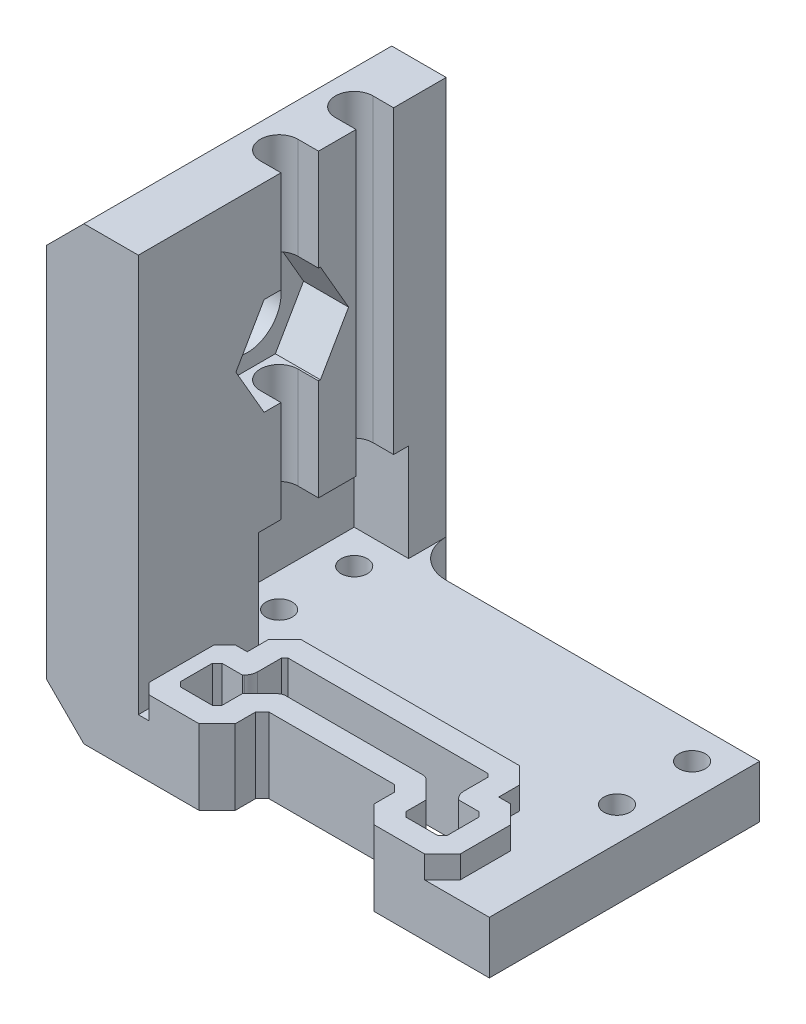
SolidWorks part; units mm, degrees
ref_plane "Front Plane" through (0, 0, 0) normal (0, 0, 1) x (1, 0, 0)
ref_plane "Top Plane" through (0, 0, 0) normal (0, 1, 0) x (1, 0, 0)
ref_plane "Right Plane" through (0, 0, 0) normal (1, 0, 0) x (0, 0, -1)
ref_plane "Plane1" through (0, 200, 0) normal (0, 1, 0) x (1, 0, 0)
sketch "Sketch1" plane through (0, 200, 0) normal (0, 1, 0) x (1, 0, 0)
  line L0 (0, -3.8557) -> (0.25, -4)
  line L1 (0.25, -4) -> (9.0787, -4)
  line L2 (10.1394, -4.4394) -> (12.5, -6.8)
  line L3 (12.5, -6.8) -> (12.5, -9.5)
  line L4 (12.5, -9.5) -> (13, -10)
  line L5 (13, -10) -> (17, -10)
  line L6 (17, -10) -> (17.5, -9.5)
  line L7 (17.5, -9.5) -> (17.5, -5.5)
  line L8 (17.5, -5.5) -> (17, -5)
  line L9 (17, -5) -> (14.3, -5)
  line L10 (14.3, -5) -> (14.0858, -4.7858)
  line L11 (13.5, -3.3716) -> (13.5, -0.3)
  line L12 (13.5, -0.3) -> (13.2, 0)
  line L13 (13.2, 0) -> (7.5, 0)
  line L14 (7.5, 0) -> (7.4, -0.1)
  line L15 (7.4, -0.1) -> (-7.4, -0.1)
  line L16 (-7.4, -0.1) -> (-7.5, 0)
  line L17 (-7.5, 0) -> (-13.2, 0)
  line L18 (-13.2, 0) -> (-13.5, -0.3)
  line L19 (-13.5, -0.3) -> (-13.5, -3.3716)
  line L20 (-14.0858, -4.7858) -> (-14.3, -5)
  line L21 (-14.3, -5) -> (-17, -5)
  line L22 (-17, -5) -> (-17.5, -5.5)
  line L23 (-17.5, -5.5) -> (-17.5, -9.5)
  line L24 (-17.5, -9.5) -> (-17, -10)
  line L25 (-17, -10) -> (-13, -10)
  line L26 (-13, -10) -> (-12.5, -9.5)
  line L27 (-12.5, -9.5) -> (-12.5, -6.8)
  line L28 (-12.5, -6.8) -> (-10.1394, -4.4394)
  line L29 (-9.0787, -4) -> (-0.25, -4)
  line L30 (-0.25, -4) -> (0, -3.8557)
  arc A0 (9.0787, -4) -> (10.1394, -4.4394) centre (9.0787, -5.5) cw
  arc A1 (14.0858, -4.7858) -> (13.5, -3.3716) centre (15.5, -3.3716) cw
  arc A2 (-13.5, -3.3716) -> (-14.0858, -4.7858) centre (-15.5, -3.3716) cw
  arc A3 (-10.1394, -4.4394) -> (-9.0787, -4) centre (-9.0787, -5.5) cw
extrude "Boss-Extrude1" add sketch "Sketch1" against normal blind 400
ref_plane "Plane2" through (0, 210, 0) normal (0, 1, 0) x (1, 0, 0)
sketch "Sketch2" plane through (0, 210, 0) normal (0, 1, 0) x (1, 0, 0)
  line L0 (-8.3538, -7.25) -> (8.3538, -7.25)
  line L1 (8.3538, -7.25) -> (9.25, -8.1462)
  line L2 (13.3036, 0.25) -> (-13.3036, 0.25)
  line L3 (-13.3036, 0.25) -> (-13.75, -0.1965)
  line L4 (-13.75, -0.1965) -> (-13.75, -3.3716)
  line L5 (-14.2626, -4.609) -> (-14.4036, -4.75)
  line L6 (-14.4036, -4.75) -> (-17.1036, -4.75)
  line L7 (-17.1036, -4.75) -> (-17.75, -5.3965)
  line L8 (-17.75, -5.3965) -> (-17.75, -9.6036)
  line L9 (-17.75, -9.6036) -> (-17.1036, -10.25)
  line L10 (-17.1036, -10.25) -> (-12.8965, -10.25)
  line L11 (-12.8965, -10.25) -> (-12.25, -9.6036)
  line L12 (-12.25, -9.6036) -> (-12.25, -6.9036)
  line L13 (-12.25, -6.9036) -> (-9.9626, -4.6162)
  line L14 (-9.0787, -4.25) -> (9.0787, -4.25)
  line L15 (9.9626, -4.6162) -> (12.25, -6.9036)
  line L16 (12.25, -6.9036) -> (12.25, -9.6036)
  line L17 (12.25, -9.6036) -> (12.8965, -10.25)
  line L18 (12.8965, -10.25) -> (17.1036, -10.25)
  line L19 (17.1036, -10.25) -> (17.75, -9.6036)
  line L20 (17.75, -9.6036) -> (17.75, -5.3965)
  line L21 (17.75, -5.3965) -> (17.1036, -4.75)
  line L22 (17.1036, -4.75) -> (14.4036, -4.75)
  line L23 (14.4036, -4.75) -> (14.2626, -4.609)
  line L24 (13.75, -3.3716) -> (13.75, -0.1965)
  line L25 (13.75, -0.1965) -> (13.3036, 0.25)
  line L26 (9.25, -8.1462) -> (9.25, -10.8462)
  line L27 (9.25, -10.8462) -> (11.6538, -13.25)
  line L28 (11.6538, -13.25) -> (18.3462, -13.25)
  line L29 (18.3462, -13.25) -> (20.75, -10.8462)
  line L30 (20.75, -10.8462) -> (20.75, -4.1538)
  line L31 (20.75, -4.1538) -> (18.3462, -1.75)
  line L32 (18.3462, -1.75) -> (16.75, -1.75)
  line L33 (16.75, -1.75) -> (16.75, -1.75)
  line L34 (16.75, -1.75) -> (16.75, 1.0462)
  line L35 (16.75, 1.0462) -> (14.5462, 3.25)
  line L36 (14.5462, 3.25) -> (-14.5462, 3.25)
  line L37 (-14.5462, 3.25) -> (-16.75, 1.0462)
  line L38 (-16.75, 1.0462) -> (-16.75, -1.75)
  line L39 (-16.75, -1.75) -> (-16.75, -1.75)
  line L40 (-16.75, -1.75) -> (-18.3462, -1.75)
  line L41 (-18.3462, -1.75) -> (-20.75, -4.1538)
  line L42 (-20.75, -4.1538) -> (-20.75, -10.8462)
  line L43 (-20.75, -10.8462) -> (-18.3462, -13.25)
  line L44 (-18.3462, -13.25) -> (-11.6538, -13.25)
  line L45 (-11.6538, -13.25) -> (-9.25, -10.8462)
  line L46 (-9.25, -10.8462) -> (-9.25, -8.1462)
  line L47 (-9.25, -8.1462) -> (-8.3538, -7.25)
  arc A0 (-14.2626, -4.609) -> (-13.75, -3.3716) centre (-15.5, -3.3716) ccw
  arc A1 (-9.0787, -4.25) -> (-9.9626, -4.6162) centre (-9.0787, -5.5) ccw
  arc A2 (9.9626, -4.6162) -> (9.0787, -4.25) centre (9.0787, -5.5) ccw
  arc A3 (13.75, -3.3716) -> (14.2626, -4.609) centre (15.5, -3.3716) ccw
  arc A4 (8.3538, -7.25) -> (8.3538, -7.25) centre (8.3538, -7.25) ccw
  arc A5 (16.75, -1.75) -> (16.75, -1.75) centre (16.75, -1.75) ccw
  arc A6 (-16.75, -1.75) -> (-16.75, -1.75) centre (-16.75, -1.75) ccw
  arc A7 (-8.3538, -7.25) -> (-8.3538, -7.25) centre (-8.3538, -7.25) ccw
  dimension "D1" = 3
extrude "Boss-Extrude2" add sketch "Sketch2" along normal blind 10 separate body
sketch "Sketch3" plane through (0, 200, 0) normal (0, 1, 0) x (1, 0, 0)
  line L0 (7.4, -0.1) -> (-7.4, -0.1) construction
  circle A0 centre (0, -0.1) radius 43.001
extrude "Cut-Extrude1" cut sketch "Sketch3" against normal blind 447.3602
sketch "Sketch4" plane through (0, 210, 0) normal (0, -1, 0) x (-1, 0, 0)
  line L0 (-13.3036, 0.25) -> (13.3036, 0.25) construction
  line L1 (27, 22.75) -> (-27, 22.75)
  line L2 (27, 22.75) -> (27, -13.25)
  line L3 (27, -13.25) -> (18.3462, -13.25)
  line L4 (-27, 22.75) -> (-27, -13.25)
  line L5 (-27, -13.25) -> (-18.3462, -13.25)
  line L25 (8.3538, -7.25) -> (9.25, -8.1462)
  line L26 (9.25, -8.1462) -> (9.25, -10.8462)
  line L27 (9.25, -10.8462) -> (11.6538, -13.25)
  line L28 (11.6538, -13.25) -> (18.3462, -13.25)
  line L29 (18.3462, -13.25) -> (20.75, -10.8462)
  line L30 (20.75, -10.8462) -> (20.75, -4.1538)
  line L31 (20.75, -4.1538) -> (18.3462, -1.75)
  line L32 (18.3462, -1.75) -> (16.75, -1.75)
  line L33 (16.75, -1.75) -> (16.75, 1.0462)
  line L34 (16.75, 1.0462) -> (14.5462, 3.25)
  line L35 (14.5462, 3.25) -> (-14.5462, 3.25)
  line L36 (-14.5462, 3.25) -> (-16.75, 1.0462)
  line L37 (-16.75, 1.0462) -> (-16.75, -1.75)
  line L38 (-16.75, -1.75) -> (-18.3462, -1.75)
  line L39 (-18.3462, -1.75) -> (-20.75, -4.1538)
  line L40 (-20.75, -4.1538) -> (-20.75, -10.8462)
  line L41 (-20.75, -10.8462) -> (-18.3462, -13.25)
  line L42 (-18.3462, -13.25) -> (-11.6538, -13.25)
  line L43 (-11.6538, -13.25) -> (-9.25, -10.8462)
  line L44 (-9.25, -10.8462) -> (-9.25, -8.1462)
  line L45 (-9.25, -8.1462) -> (-8.3538, -7.25)
  line L46 (-8.3538, -7.25) -> (8.3538, -7.25)
  line L47 (8.3538, -7.25) -> (9.25, -8.1462)
  line L48 (9.25, -8.1462) -> (9.25, -10.8462)
  line L49 (9.25, -10.8462) -> (11.6538, -13.25)
  line L50 (11.6538, -13.25) -> (18.3462, -13.25)
  line L51 (18.3462, -13.25) -> (20.75, -10.8462)
  line L52 (20.75, -10.8462) -> (20.75, -4.1538)
  line L53 (20.75, -4.1538) -> (18.3462, -1.75)
  line L54 (18.3462, -1.75) -> (16.75, -1.75)
  line L55 (16.75, -1.75) -> (16.75, 1.0462)
  line L56 (16.75, 1.0462) -> (14.5462, 3.25)
  line L57 (14.5462, 3.25) -> (-14.5462, 3.25)
  line L58 (-14.5462, 3.25) -> (-16.75, 1.0462)
  line L59 (-16.75, 1.0462) -> (-16.75, -1.75)
  line L60 (-16.75, -1.75) -> (-18.3462, -1.75)
  line L61 (-18.3462, -1.75) -> (-20.75, -4.1538)
  line L62 (-20.75, -4.1538) -> (-20.75, -10.8462)
  line L63 (-20.75, -10.8462) -> (-18.3462, -13.25)
  line L64 (-18.3462, -13.25) -> (-11.6538, -13.25)
  line L65 (-11.6538, -13.25) -> (-9.25, -10.8462)
  line L66 (-9.25, -10.8462) -> (-9.25, -8.1462)
  line L67 (-9.25, -8.1462) -> (-8.3538, -7.25)
  line L68 (-8.3538, -7.25) -> (8.3538, -7.25)
  point P8 (0, 22.75)
  point P29 (0, 0.25)
  dimension "D2" = 19.5
  dimension "D3" = 54
  dimension "D4" = 0
  dimension "D1" = 0
extrude "Boss-Extrude3" add sketch "Sketch4" against normal blind 7
sketch "Sketch5" plane through (0, 210, 0) normal (0, -1, 0) x (-1, 0, 0)
  line L0 (0, 22.75) -> (0, 9.6848) construction
  line L1 (27, 22.75) -> (-27, 22.75) construction
  line L2 (27, 22.75) -> (27, -13.25) construction
  circle A0 centre (22.5, 18.25) radius 1.75
  circle A1 centre (22.5, 8.25) radius 1.75
  circle A2 centre (-22.5, 8.25) radius 1.75
  circle A3 centre (-22.5, 18.25) radius 1.75
  dimension "D4" = 3.5
  dimension "D1" = 10
  dimension "D2" = 4.5
  dimension "D3" = 4.5
extrude "Cut-Extrude2" cut sketch "Sketch5" against normal blind 33
sketch "Sketch6" plane through (-27, 0, 0) normal (-1, 0, 0) x (0, 0, 1)
  line L1 (-22.75, 210) -> (13.25, 210)
  line L2 (-22.75, 210) -> (-22.75, 270)
  line L3 (-22.75, 270) -> (13.25, 270)
  line L4 (13.25, 210) -> (13.25, 270)
  dimension "D1" = 60
extrude "Boss-Extrude4" add sketch "Sketch6" along normal blind 5
sketch "Sketch7" plane through (0, 217, 0) normal (0, 1, 0) x (1, 0, 0)
  line L0 (-20.75, -10.8462) -> (-20.75, -4.1538) construction
  line L1 (-27, -13.25) -> (-19.75, -13.25)
  line L2 (-27, -13.25) -> (-27, 2.75)
  line L3 (-27, 2.75) -> (-19.75, 2.75)
  line L4 (-19.75, -13.25) -> (-19.75, 2.75)
  dimension "D1" = 1
  dimension "D2" = 16
extrude "Boss-Extrude5" add sketch "Sketch7" along normal up to surface (53 mm away) up to face at (-29.5, 270, -4.75)
sketch "Sketch8" plane through (0, 0, -22.75) normal (0, 0, -1) x (-1, 0, 0)
  line L0 (32, 210) -> (-27, 210) construction
  line L1 (32, 270) -> (19.75, 270)
  line L2 (32, 270) -> (32, 210)
  line L3 (32, 210) -> (19.75, 210)
  line L4 (19.75, 270) -> (19.75, 210)
  dimension "D1" = 0
extrude "Boss-Extrude6" add sketch "Sketch8" along normal blind 5
fillet "Fillet1" radius 5 1 edges at (-19.75, 213.5, -22.75)
sketch "Sketch10" plane through (-27, 0, 0) normal (1, 0, 0) x (0, 0, -1)
  line L0 (22.75, 270) -> (22.75, 217) construction
  line L1 (2.75, 270) -> (22.75, 270)
  line L2 (2.75, 270) -> (2.75, 230)
  line L3 (2.75, 230) -> (22.75, 230)
  line L4 (22.75, 270) -> (22.75, 230)
  dimension "D1" = 40
extrude "Boss-Extrude7" add sketch "Sketch10" along normal up to surface (7.25 mm away) up to face at (-19.75, 231, 6.375)
sketch "Sketch9" plane through (-19.75, 0, 0) normal (1, 0, 0) x (0, 0, -1)
  line L0 (-13.25, 250) -> (27.75, 250) construction
  line L1 (14.7555, 250) -> (11.0027, 256.5)
  line L2 (11.0027, 256.5) -> (3.4972, 256.5)
  line L3 (3.4972, 256.5) -> (-0.2556, 250)
  line L4 (-0.2556, 250) -> (3.4972, 243.5)
  line L5 (3.4972, 243.5) -> (11.0027, 243.5)
  line L6 (11.0027, 243.5) -> (14.7555, 250)
  line L8 (-13.25, 270) -> (-13.25, 217) construction
  line L9 (27.75, 270) -> (27.75, 217) construction
  line L10 (27.75, 270) -> (-13.25, 270) construction
  circle A0 centre (7.25, 250) radius 6.5 construction
  dimension "D1" = 13
  dimension "D2" = 20
extrude "Cut-Extrude3" cut sketch "Sketch9" against normal blind 6
sketch "Sketch11" plane through (0, 217, 0) normal (0, 1, 0) x (1, 0, 0)
  line L0 (-22.5, 20.75) -> (-17.8248, 20.75)
  line L1 (-17.8248, 20.75) -> (-17.8248, 15.75)
  line L2 (-17.8248, 15.75) -> (-22.5, 15.75)
  line L3 (-22.5, 10.75) -> (-17.8248, 10.75)
  line L4 (-17.8248, 10.75) -> (-17.8248, 5.75)
  line L5 (-17.8248, 5.75) -> (-22.5, 5.75)
  arc A0 (-22.5, 20.75) -> (-22.5, 15.75) centre (-22.5, 18.25) ccw
  arc A1 (-22.5, 10.75) -> (-22.5, 5.75) centre (-22.5, 8.25) ccw
  dimension "D1" = 5
  dimension "D2" = 5
extrude "Cut-Extrude4" cut sketch "Sketch11" along normal through all
sketch "Sketch12" plane through (-25.75, 0, 0) normal (1, 0, 0) x (0, 0, -1)
  line L0 (14.7555, 250) -> (-0.2556, 250) construction
  circle A0 centre (7.25, 250) radius 4.5
  dimension "D1" = 9
extrude "Cut-Extrude5" cut sketch "Sketch12" against normal blind 16
chamfer "Chamfer2" distance 5 angle 45 1 edges at (-32, 270, -7.25)
chamfer "Chamfer3" distance 5 angle 45 1 edges at (-32, 210, -7.25)
sketch "Sketch13" plane through (-32, 0, 0) normal (-1, 0, 0) x (0, 0, 1)
  circle A0 centre (-7.25, 250) radius 4.5
  circle A1 centre (-7.25, 250) radius 6.5
  dimension "D1" = 2
extrude "Boss-Extrude8" add sketch "Sketch13" along normal blind 2
fillet "Fillet2" radius 1 1 edges at (-32, 250, -13.75)
